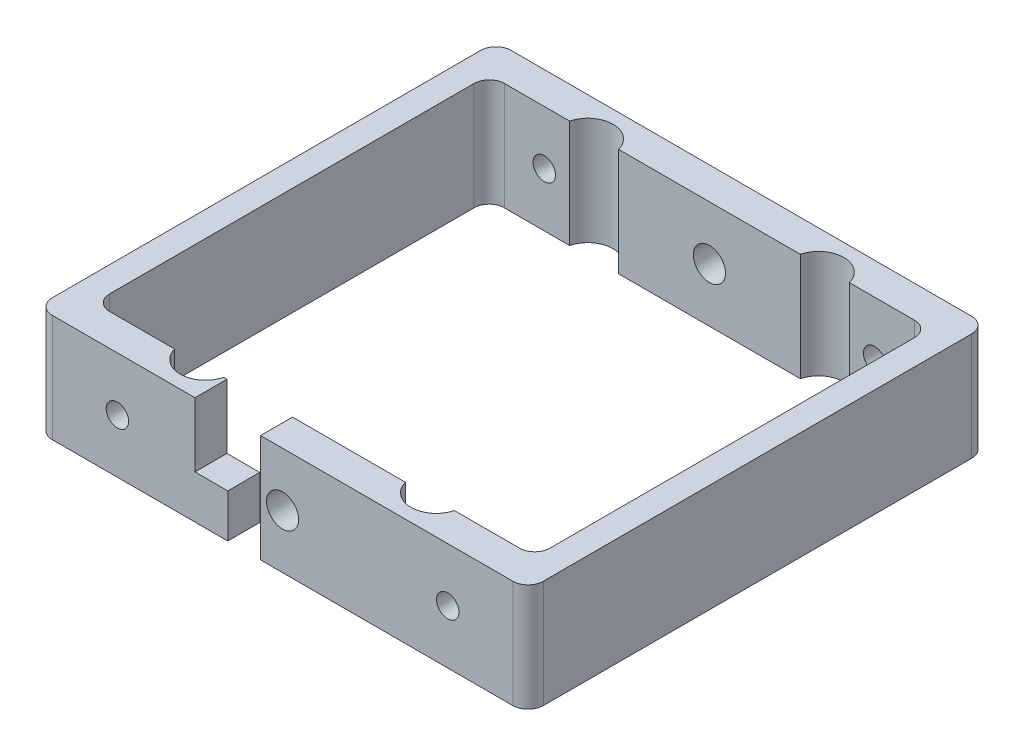
SolidWorks part; units mm, degrees
ref_plane "Front Plane" through (0, 0, 0) normal (0, 0, 1) x (1, 0, 0)
ref_plane "Top Plane" through (0, 0, 0) normal (0, 1, 0) x (1, 0, 0)
ref_plane "Right Plane" through (0, 0, 0) normal (1, 0, 0) x (0, 0, -1)
sketch "Sketch1" plane through (0, 0, 0) normal (0, 1, 0) x (1, 0, 0)
  line L1 (0, 0) -> (60, 0)
  line L2 (0, 0) -> (0, -6.32)
  line L3 (0, -6.32) -> (60, -6.32)
  line L4 (60, 0) -> (60, -6.32)
  dimension "D1" = 60
  dimension "D2" = 6.32
extrude "Boss-Extrude1" add sketch "Sketch1" along normal mid plane 21.28
sketch "Sketch2" plane through (0, 10.64, 0) normal (0, 1, 0) x (1, 0, 0)
  line L0 (0, 0) -> (0, -6.32) construction
  line L1 (0, -6.32) -> (60, -6.32) construction
  line L2 (60, -6.32) -> (60, 0) construction
  circle A0 centre (7.21, 1.25) radius 5
  circle A1 centre (52.79, 1.25) radius 5
  dimension "D1" = 7.21
  dimension "D3" = 7.21
  dimension "D2" = 7.57
  dimension "D4" = 7.57
extrude "Cut-Extrude1" cut sketch "Sketch2" against normal through all
sketch "Sketch3" plane through (60, 0, 0) normal (1, 0, 0) x (0, 0, -1)
  line L1 (-6.32, 10.64) -> (0, 10.64)
  line L2 (-6.32, 10.64) -> (-6.32, -10.64)
  line L3 (-6.32, -10.64) -> (0, -10.64)
  line L4 (0, 10.64) -> (0, -10.64)
extrude "Boss-Extrude2" add sketch "Sketch3" along normal blind 18.5
sketch "Sketch4" plane through (0, 0, 0) normal (-1, 0, 0) x (0, 0, 1)
  line L1 (0, 10.64) -> (6.32, 10.64)
  line L2 (0, 10.64) -> (0, -10.64)
  line L3 (0, -10.64) -> (6.32, -10.64)
  line L4 (6.32, 10.64) -> (6.32, -10.64)
extrude "Boss-Extrude3" add sketch "Sketch4" along normal blind 18.5
sketch "Sketch5" plane through (0, 0, 0) normal (0, 0, -1) x (-1, 0, 0)
  line L5 (-2.3688, -10.64) -> (18.5, -10.64) construction
  line L6 (18.5, 10.64) -> (13.5, 10.64)
  line L7 (18.5, 10.64) -> (18.5, -10.64)
  line L8 (18.5, -10.64) -> (13.5, -10.64)
  line L9 (13.5, 10.64) -> (13.5, -10.64)
  dimension "D1" = 5
extrude "Boss-Extrude6" add sketch "Sketch5" along normal blind 84.33
sketch "Sketch6" plane through (0, 0, 0) normal (0, 0, -1) x (-1, 0, 0)
  line L1 (-78.5, 10.64) -> (-73.5, 10.64)
  line L2 (-78.5, 10.64) -> (-78.5, -10.652)
  line L3 (-78.5, -10.652) -> (-73.5, -10.652)
  line L4 (-73.5, 10.64) -> (-73.5, -10.652)
  dimension "D1" = 5
extrude "Boss-Extrude7" add sketch "Sketch6" along normal blind 84.33
sketch "Sketch7" plane through (73.5, 0, 0) normal (-1, 0, 0) x (0, 0, 1)
  line L0 (-84.33, -10.652) -> (0, -10.652) construction
  line L1 (-84.33, 10.64) -> (-78.01, 10.64)
  line L2 (-84.33, 10.64) -> (-84.33, -10.652)
  line L3 (-84.33, -10.652) -> (-78.01, -10.652)
  line L4 (-78.01, 10.64) -> (-78.01, -10.652)
  dimension "D1" = 6.32
extrude "Boss-Extrude8" add sketch "Sketch7" along normal through all
sketch "Sketch9" plane through (0, 10.64, 0) normal (0, 1, 0) x (1, 0, 0)
  line L0 (-18.5, 84.33) -> (78.5, 84.33) construction
  circle A0 centre (7.21, 76.76) radius 5
  circle A1 centre (52.79, 76.76) radius 5
  dimension "D1" = 7.57
  dimension "D2" = 7.57
  dimension "D3" = 10
extrude "Cut-Extrude2" cut sketch "Sketch9" against normal through all
sketch "Sketch10" plane through (0, 0, -84.33) normal (0, 0, -1) x (-1, 0, 0)
  line L1 (-78.5, -10.64) -> (18.5, -10.64) construction
  line L2 (-30, -10.64) -> (-30, 10.64) construction
  line L3 (18.5, 10.64) -> (-78.5, 10.64) construction
  circle A0 centre (-62.6312, 0.005) radius 2.22
  circle A1 centre (2.6312, 0.005) radius 2.22
  dimension "D1" = 5
  dimension "D2" = 10.645
extrude "Cut-Extrude3" cut sketch "Sketch10" against normal through all
fillet "Fillet1" radius 3 8 edges at (-18.5, 0, 6.32) (78.5, 0, 6.32) (78.5, -0.006, -84.33) (-18.5, -0.006, -84.33) (-13.5, 0, -78.01) (-13.5, 0, 0) (73.5, -0.006, -78.01) (73.5, 0, 0)
sketch "Sketch13" plane through (0, 0, -84.33) normal (0, 0, -1) x (-1, 0, 0)
  line L1 (-75.5, 10.64) -> (-75.5, -10.652) construction
  line L2 (-75.5, -10.64) -> (15.5, -10.64) construction
  circle A0 centre (-30, 0.005) radius 3.175
  dimension "D1" = 45.5
  dimension "D3" = 6.35
  dimension "D2" = 10.645
extrude "Cut-Extrude4" cut sketch "Sketch13" against normal through all
sketch "Sketch16" plane through (0, -10.652, 0) normal (0, -1, 0) x (1, 0, 0)
  line L6 (75.5, -84.33) -> (-15.5, -84.33) construction
  line L7 (25.5729, -84.33) -> (12.6189, -84.33)
  line L8 (25.5729, -84.33) -> (25.5729, -78.01)
  line L9 (25.5729, -78.01) -> (12.6189, -78.01)
  line L10 (12.6189, -84.33) -> (12.6189, -78.01)
  line L11 (12.0512, -78.01) -> (47.9488, -78.01) construction
  dimension "D1" = 12.954
extrude "Cut-Extrude6" [suppressed] cut sketch "Sketch16" against normal mid plane 25.4
sketch "Sketch17" plane through (0, 10.64, 0) normal (0, 1, 0) x (1, 0, 0)
  line L1 (12.6964, 0.5862) -> (25.6504, 0.5862)
  line L2 (12.6964, 0.5862) -> (12.6964, -6.4457)
  line L3 (12.6964, -6.4457) -> (25.6504, -6.4457)
  line L4 (25.6504, 0.5862) -> (25.6504, -6.4457)
  dimension "D1" = 12.954
extrude "Cut-Extrude7" cut sketch "Sketch17" against normal mid plane 25.4
sketch "Sketch18" plane through (0, 0, 6.32) normal (0, 0, 1) x (1, 0, 0)
  line L0 (12.6964, -2.06) -> (25.6504, -2.06) construction
  line L1 (19.1734, -2.06) -> (25.6504, -2.06)
  line L2 (19.1734, -2.06) -> (19.1734, -10.64)
  line L3 (19.1734, -10.64) -> (25.6504, -10.64)
  line L4 (25.6504, -2.06) -> (25.6504, -10.64)
  line L5 (-15.5, -10.64) -> (75.5, -10.64) construction
extrude "Cut-Extrude8" cut sketch "Sketch18" against normal up to next
